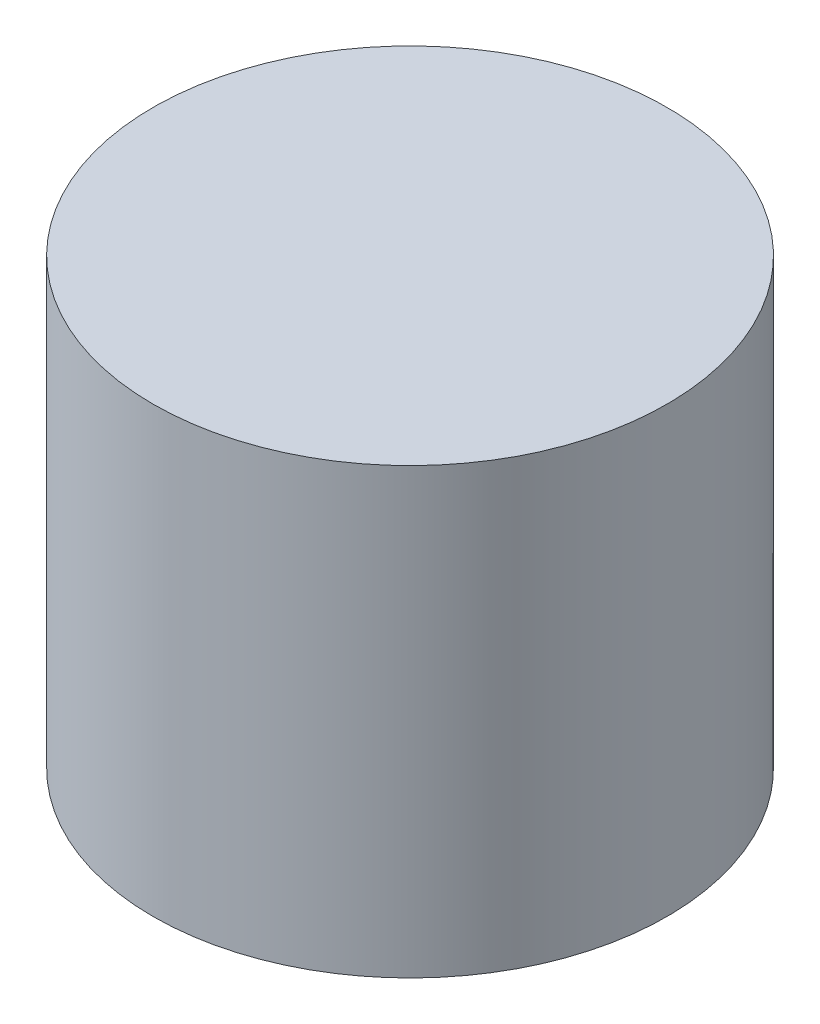
SolidWorks part; units mm, degrees
ref_plane "Front Plane" through (0, 0, 0) normal (0, 0, 1) x (1, 0, 0)
ref_plane "Top Plane" through (0, 0, 0) normal (0, 1, 0) x (1, 0, 0)
ref_plane "Right Plane" through (0, 0, 0) normal (1, 0, 0) x (0, 0, -1)
sketch "Sketch2" plane through (0, 0, 0) normal (0, 1, 0) x (1, 0, 0)
  circle A0 centre (0, 0) radius 6.95
  point P3 (0, 0)
  dimension "D1" = 13.9
extrude "Boss-Extrude1" add sketch "Sketch2" along normal blind 12
